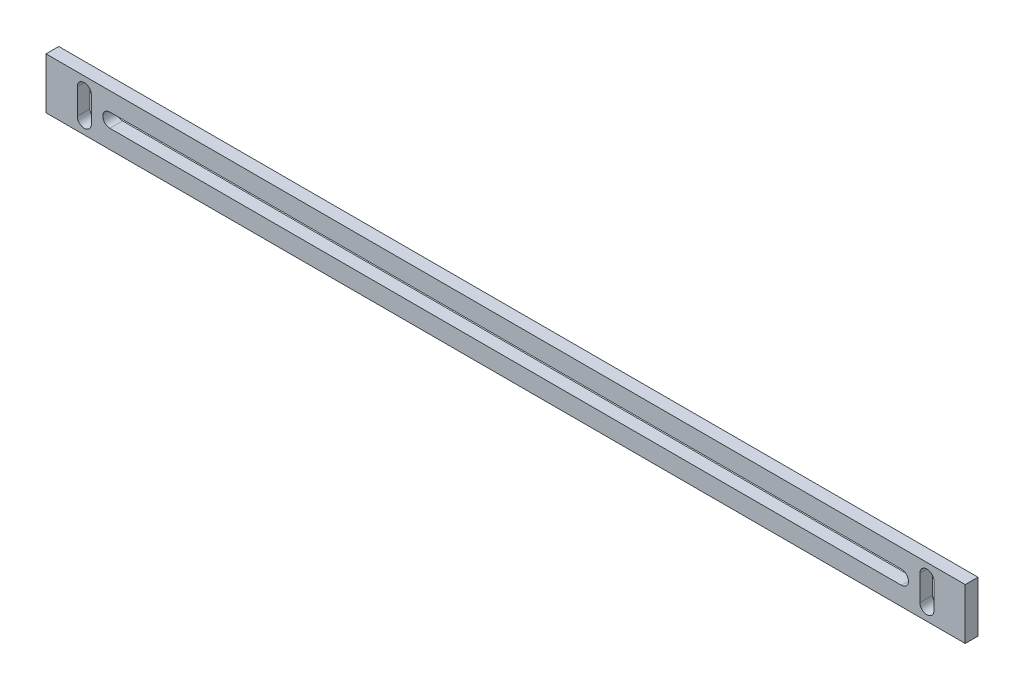
SolidWorks part; units mm, degrees
material "ABS"
ref_plane "前视基准面" through (0, 0, 0) normal (0, 0, 1) x (1, 0, 0)
ref_plane "上视基准面" through (0, 0, 0) normal (0, 1, 0) x (1, 0, 0)
ref_plane "右视基准面" through (0, 0, 0) normal (1, 0, 0) x (0, 0, -1)
other "Configuration Table"
sketch "草图1" plane through (0, 0, 0) normal (0, 0, 1) x (1, 0, 0)
  line L0 (0, 0) -> (0, 10)
  line L1 (0, 10) -> (-175, 10)
  line L2 (-175, 10) -> (-175, -10)
  line L3 (-175, -10) -> (175, -10)
  line L4 (175, -10) -> (175, 10)
  line L5 (175, 10) -> (0, 10)
extrude "凸台-拉伸1" add sketch "草图1" along normal blind 5 contours L4 L5 L1 L2 L3 region at (87.5, 6.4943, 0)
sketch "草图3" plane through (0, 0, 0) normal (0, 0, -1) x (-1, 0, 0)
  line L0 (-175, 0) -> (-165, 0)
  line L1 (-175, -10) -> (-175, 10) construction
  line L2 (-165, 0) -> (-165, 10)
  line L3 (-175, 10) -> (175, 10) construction
  line L4 (-165, 0) -> (-165, -10)
  line L5 (175, -10) -> (-175, -10) construction
  line L6 (-165, 0) -> (-155, 0)
  line L7 (175, 0) -> (165, 0)
  line L8 (175, 10) -> (175, -10) construction
  line L9 (165, 0) -> (165, 10)
  line L10 (165, 0) -> (165, -10)
  line L11 (165, 0) -> (155, 0)
  line L12 (155, 0) -> (-155, 0)
  line L13 (-155, 0) -> (155, 0) construction
  line L14 (-155, 2.75) -> (155, 2.75)
  line L15 (-155, -2.75) -> (155, -2.75)
  line L16 (-165, 0) -> (-165, -5)
  line L17 (-165, -5) -> (-165, 5)
  line L18 (165, -5) -> (165, 5)
  line L19 (-165, -5) -> (-165, 5) construction
  line L20 (-167.75, -5) -> (-167.75, 5)
  line L21 (-162.25, -5) -> (-162.25, 5)
  line L22 (165, -5) -> (165, 5) construction
  line L23 (162.25, -5) -> (162.25, 5)
  line L24 (167.75, -5) -> (167.75, 5)
  arc A0 (-155, 2.75) -> (-155, -2.75) centre (-155, 0) ccw
  arc A1 (155, -2.75) -> (155, 2.75) centre (155, 0) ccw
  arc A2 (-167.75, -5) -> (-162.25, -5) centre (-165, -5) ccw
  arc A3 (-162.25, 5) -> (-167.75, 5) centre (-165, 5) ccw
  arc A4 (162.25, -5) -> (167.75, -5) centre (165, -5) ccw
  arc A5 (167.75, 5) -> (162.25, 5) centre (165, 5) ccw
  point P19 (0, 0)
  point P28 (-165, 0)
  point P33 (165, 0)
  dimension "D1" = 10
  dimension "D2" = 10
  dimension "D3" = 10
  dimension "D4" = 10
extrude "切除-拉伸1" cut sketch "草图3" against normal blind 5 contours L21 A3 L2 L6 | L2 A3 L20 L0 | L20 A2 L4 L0 | L4 A2 L21 L6 | L15 A1 L11 L12 L6 A0 | L11 A1 L14 A0 L6 L12 | L24 A5 L9 L7 | L9 A5 L23 L11 | L23 A4 L10 L11 | L10 A4 L24 L7 region at (166.3123, 3.6062, 0) region at (166.3123, -3.6062, 0) region at (-163.6877, 3.6062, 0) region at (-163.6877, -3.6062, 0) region at (0, 1.3721, 0) region at (0, -1.3721, 0) region at (163.6877, -3.6062, 0) region at (163.6877, 3.6062, 0) region at (-166.3123, 3.6062, 0) region at (-166.3123, -3.6062, 0)
sketch "草图4" plane through (0, 0, 0) normal (0, 0, -1) x (-1, 0, 0)
  line L0 (-175, -10) -> (-180, -10)
  line L1 (-180, -10) -> (-180, 10)
  line L2 (-180, 10) -> (-175, 10)
  line L3 (-175, 10) -> (-175, -10)
  line L4 (175, -10) -> (180, -10)
  line L5 (180, -10) -> (180, 10)
  line L6 (180, 10) -> (175, 10)
  line L7 (175, 10) -> (175, -10)
extrude "凸台-拉伸2" add sketch "草图4" against normal blind 5
